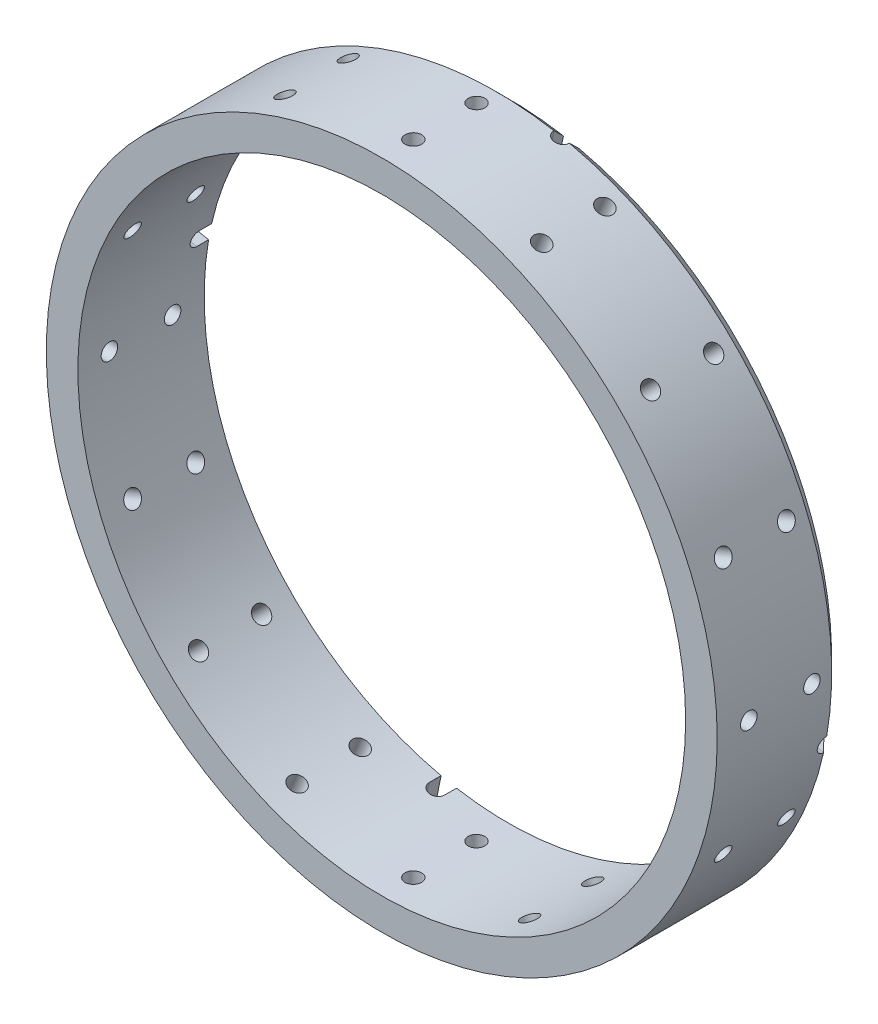
SolidWorks part; units mm, degrees
ref_plane "Płaszczyzna przednia" through (0, 0, 0) normal (0, 0, 1) x (1, 0, 0)
ref_plane "Płaszczyzna górna" through (0, 0, 0) normal (0, 1, 0) x (1, 0, 0)
ref_plane "Płaszczyzna prawa" through (0, 0, 0) normal (1, 0, 0) x (0, 0, -1)
sketch "Szkic1" plane through (0, 0, 0) normal (0, 0, 1) x (1, 0, 0)
  circle A0 centre (0, 0) radius 85
  circle A1 centre (0, 0) radius 77
  point P4 (0, 0)
  dimension "D1" = 170
  dimension "D2" = 8
extrude "Dodanie-wyciągnięcie1" add sketch "Szkic1" along normal blind 32
sketch "Szkic2" plane through (0, 0, 32) normal (0, 0, 1) x (1, 0, 0)
  line L0 (0, 46.3429) -> (0, 98.4468) construction
  circle A0 centre (0, 0) radius 85 construction
  circle A1 centre (0, 0) radius 85
  point P6 (0, 85)
sketch3d "Szkic 3D1"
sketch "Szkic3" plane through (0, 85, 0) normal (0, 1, 0) x (1, 0, 0)
  line L0 (0, 18.1334) -> (0, -45.2976) construction
  line L1 (77, 0) -> (-77, 0) construction
  circle A0 centre (0, -8) radius 2.1
  circle A1 centre (0, -24) radius 2.1
  dimension "D1" = 4.2
  dimension "D2" = 4.2
  dimension "D3" = 8
  dimension "D4" = 16
extrude "Wytnij-wyciągnięcie1" cut sketch "Szkic3" against normal blind 32
pattern_circular "Szyk kołowy1" count 16 over 360 about axis through (0, 0, 32) along (0, 0, -1) of "Wytnij-wyciągnięcie1" reverse direction yes
chamfer "Sfazowanie1" distance 3 angle 45 1 edges at (85, 0, 0)
sketch "Szkic5" plane through (0, 0, 0) normal (0, 0, -1) x (-1, 0, 0)
  line L0 (0, 109.5264) -> (0, 0) construction
  line L1 (-23.4011, 117.6453) -> (0, 0) construction
  line L2 (-18.5397, 82.9535) -> (-16.9785, 75.1048)
  line L3 (-14.6165, 83.7338) -> (-13.0553, 75.8852)
  line L5 (-21.4395, 118.0355) -> (1.9616, 0.3902) construction
  line L6 (-25.3627, 117.2552) -> (-1.9616, -0.3902) construction
  circle A0 centre (0, 0) radius 85 construction
  circle A1 centre (0, 0) radius 77 construction
  arc A2 (-14.6165, 83.7338) -> (-18.5397, 82.9535) centre (0, 0) ccw
  arc A3 (-13.0553, 75.8852) -> (-16.9785, 75.1048) centre (0, 0) ccw
  dimension "D1" = 11.25
  dimension "D2" = 2
  dimension "D3" = 2
extrude "Wytnij-wyciągnięcie2" cut sketch "Szkic5" against normal blind 5
fillet "Zaokrąglenie2" radius 2 2 edges at (13.8359, 79.8095, 5) (17.7591, 79.0291, 5)
pattern_circular "Szyk kołowy4" count 4 over 360 about axis through (0, 0, 32) along (0, 0, -1) of "Zaokrąglenie2", "Wytnij-wyciągnięcie2" reverse direction yes
